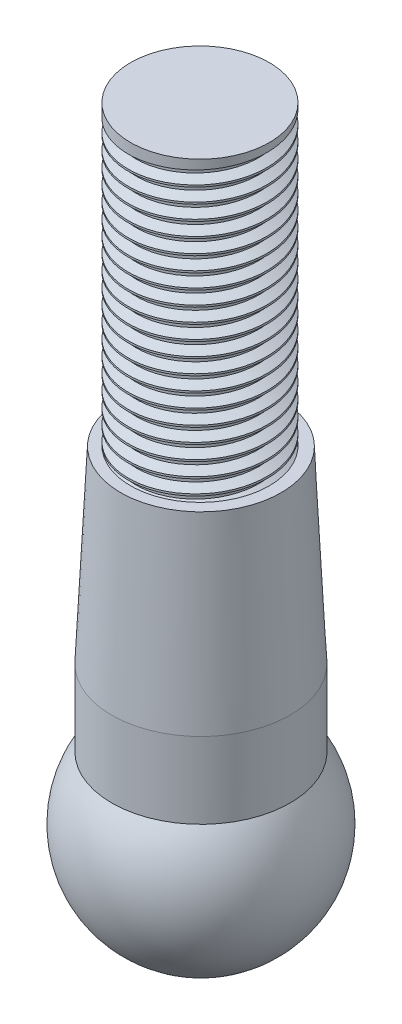
SolidWorks part; units mm, degrees
ref_plane "Płaszczyzna przednia" through (0, 0, 0) normal (0, 0, 1) x (1, 0, 0)
ref_plane "Płaszczyzna górna" through (0, 0, 0) normal (0, 1, 0) x (1, 0, 0)
ref_plane "Płaszczyzna prawa" through (0, 0, 0) normal (1, 0, 0) x (0, 0, -1)
sketch "Szkic1" plane through (0, 0, 0) normal (0, 0, 1) x (1, 0, 0)
  line L0 (0, -11) -> (0, 11)
  arc A0 (0, -11) -> (0, 11) centre (0, 0) ccw
  dimension "D1" = 22
revolve "Obrót1" add sketch "Szkic1" angle 360 about L0
ref_plane "Płaszczyzna1" through (0, 11, 0) normal (0, 1, 0) x (1, 0, 0)
sketch "Szkic2" plane through (0, 11, 0) normal (0, 1, 0) x (1, 0, 0)
  circle A0 centre (0, 0) radius 9
  dimension "D1" = 18
extrude "Dodanie-wyciągnięcie1" add sketch "Szkic2" along normal blind 3 and the other way up to next contours A0
sketch "Szkic3" plane through (0, 0, 0) normal (0, 0, 1) x (1, 0, 0)
  line L0 (0, 33) -> (0, 14)
  line L1 (0, 14) -> (-9, 14)
  line L2 (-9, 14) -> (-8.1, 33)
  line L3 (-8.1, 33) -> (0, 33)
  line L6 (9, 14) -> (-9, 14) construction
  dimension "D1" = 19
  dimension "D2" = 8.1
  dimension "D3" = 9
revolve "Obrót2" add sketch "Szkic3" angle 360 about L0
sketch "Szkic4" plane through (0, 0, 0) normal (0, 0, 1) x (1, 0, 0)
  line L1 (-0.1, 33) -> (-7.1, 33)
  line L2 (-0.1, 33) -> (-0.1, 63)
  line L3 (-0.1, 63) -> (-7.1, 63)
  line L4 (-7.1, 33) -> (-7.1, 63)
  line L5 (8.1, 33) -> (-8.1, 33) construction
  dimension "D1" = 7
  dimension "D2" = 30
  dimension "D3" = 1
revolve "Obrót3" add sketch "Szkic4" angle 360 about L2
thread "Gwint1" pitch 1.5 method cut profile "Profil gwintu1" start angle 0, offset 0, length 30, pitch 1.5, diameter 14
ref_plane "Płaszczyzna2" through (-7.1, 63, 0) normal (0, 0, 1) x (-1, 0, 0)
sketch "Profil gwintu1" plane through (-7.1, 63, 0) normal (0, 0, 1) x (-1, 0, 0)
  line L0 (0, 0) -> (0, 1.5) construction
  line L11 (0, 0) -> (0, 1.3125)
  line L12 (0, 1.3125) -> (-0.8119, 0.8437)
  line L13 (-0.8119, 0.8437) -> (-0.8119, 0.4687)
  line L15 (-0.8119, 0.4687) -> (0, 0)
  line L17 (-0.8119, 0.6562) -> (0, 0.6562) construction
  point P2 (0, 0)
  dimension "Pitch" = 1.5
  dimension "Profile_Angle" = 60
  dimension "Profile_Land" = 0.375
  dimension "Profile_Height" = 0.8119
